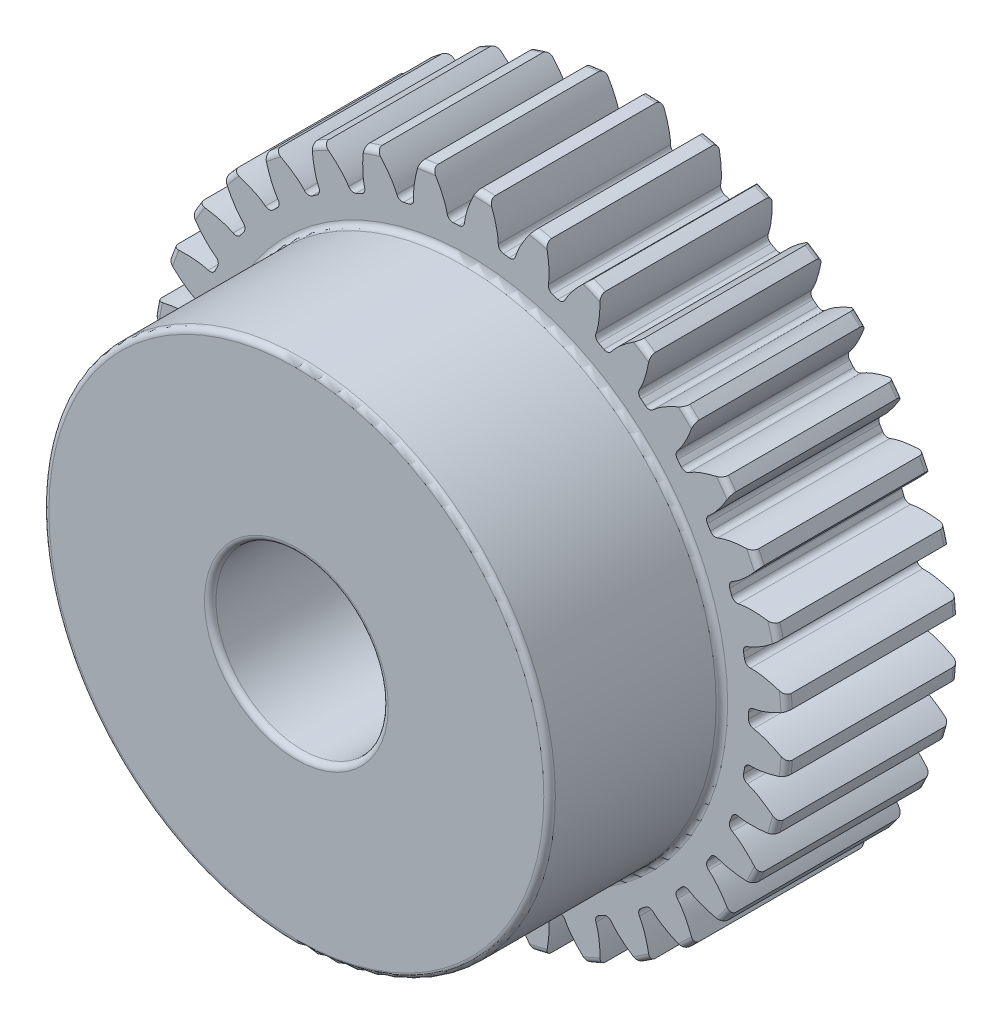
SolidWorks part; units mm, degrees
ref_plane "Front Plane" through (0, 0, 0) normal (0, 0, 1) x (1, 0, 0)
ref_plane "Top Plane" through (0, 0, 0) normal (0, 1, 0) x (1, 0, 0)
ref_plane "Right Plane" through (0, 0, 0) normal (1, 0, 0) x (0, 0, -1)
sketch "Sketch1" plane through (0, 0, 0) normal (0, 0, 1) x (1, 0, 0)
  line L0 (0, 0) -> (0, 22.225) construction
  line L1 (-7.143, 24.8248) -> (7.143, 19.6252) construction
  circle A0 centre (0, 0) radius 20.6375 construction
  circle A1 centre (0, 0) radius 23.495 construction
  circle A2 centre (0, 0) radius 22.225 construction
  circle A3 centre (0, 0) radius 20.8847 construction
  circle A4 centre (0, 0) radius 6.35 construction
  circle A5 centre (0, 0) radius 18.669 construction
  point P8 (254, 0)
  point P13 (444.5, 0)
  dimension "OD | Outside Diameter" = 46.99
  dimension "Root Diameter" = 41.275
  dimension "Gear Pitch Diameter" = 44.45
  dimension "Base Diameter" = 41.7693
  dimension "For Shaft Diameter" = 12.7
  dimension "Hub Diameter" = 37.338
  dimension "Pressure Angle" = 20
  dimension "Number of Teeth" = 889
  dimension "Gear Pitch | Diametral Pitch" = 508
sketch "Sketch2" plane through (0, 0, 0) normal (1, 0, 0) x (0, 0, -1)
  line L0 (-12.7, 0) -> (12.7, 0) construction
  line L1 (-12.7, 23.495) -> (12.7, 23.495) construction
  point P2 (0, 23.495)
  point P4 (0, 0)
  point P6 (0, 23.495)
  dimension "Overall Width" = 25.4
  dimension "Hub Width" = 12.7
  dimension "Face Width" = 12.7
sketch "Sketch3" plane through (0, 0, 0) normal (0, 0, 1) x (1, 0, 0)
  circle A0 centre (0, 0) radius 23.495
  circle A1 centre (0, 0) radius 23.495 construction
extrude "Boss-Extrude1" add sketch "Sketch3" against normal up to vertex (12.7 mm away) and the other way up to vertex (12.7 mm away) up to point (0, 0, -12.7) other way up to point (0, 0, 12.7)
sketch "Sketch5" plane through (0, 0, 0) normal (1, 0, 0) x (0, 0, -1)
  line L1 (-12.7, 23.495) -> (0, 23.495)
  line L2 (-12.7, 23.495) -> (-12.7, 18.669)
  line L3 (-12.7, 18.669) -> (0, 18.669)
  line L4 (0, 23.495) -> (0, 18.669)
  line L11 (12.7, 6.35) -> (-12.7, 6.35)
  line L12 (12.7, 6.35) -> (12.7, 0)
  line L13 (12.7, 0) -> (-12.7, 0)
  line L14 (-12.7, 6.35) -> (-12.7, 0)
  point P5 (0, 6.35)
  point P12 (0, 18.669)
revolve "Cut-Revolve1" cut sketch "Sketch5" angle 360 about L0
fillet "Fillet2" radius 0.4261 6 edges at (23.495, 0, -12.7) (6.35, 0, -12.7) (6.35, 0, 12.7) (18.669, 0, 0) (23.495, 0, 0) (18.669, 0, 12.7)
sketch "Sketch4" plane through (0, 0, 0) normal (0, 0, 1) x (1, 0, 0)
  line L0 (0, 0) -> (20.6282, 0.6185) construction
  line L2 (0, 0) -> (20.6282, -0.6185) construction
  line L4 (20.6282, 0.6185) -> (20.8753, 0.6259)
  line L5 (20.8753, -0.6259) -> (20.6282, -0.6185)
  arc A0 (20.6282, 0.6185) -> (20.6282, -0.6185) centre (0, 0) cw
  arc A3 (23.4383, 1.631) -> (23.4383, -1.631) centre (0, 0) cw
  circle A4 centre (0, 0) radius 23.495 construction
  spline S0 degree 4 poles (20.8753, 0.6259) (20.8794, 0.6261) (20.8909, 0.6267) (20.9126, 0.6284) (20.9479, 0.632) (20.993, 0.6376) (21.0511, 0.6462) (21.1194, 0.6581) (21.1944, 0.6729) (21.2759, 0.6908) (21.357, 0.7105) (21.4378, 0.7316) (21.5182, 0.7541) (21.6154, 0.783) (21.7317, 0.8199) (21.8673, 0.8665) (22.0206, 0.9233) (22.1763, 0.9855) (22.3291, 1.0501) (22.4829, 1.1195) (22.6314, 1.1894) (22.785, 1.2661) (22.9265, 1.3391) (23.0844, 1.4253) (23.2115, 1.4962) (23.3785, 1.5946) (23.4769, 1.6542) (23.5918, 1.7255) (23.6426, 1.7581) (23.674, 1.7781) knots 0 0 0 0 0 0.005377 0.015084 0.028532 0.04661 0.064855 0.092111 0.119476 0.146842 0.174209 0.201575 0.228941 0.256307 0.307035 0.361767 0.4165 0.471232 0.525964 0.580697 0.635429 0.690161 0.744894 0.799626 0.854358 0.909091 0.954545 1 1 1 1 1 construction
  spline S1 degree 4 poles (20.8753, 0.6259) (20.8794, 0.6261) (20.8909, 0.6267) (20.9126, 0.6284) (20.9479, 0.632) (20.993, 0.6376) (21.0511, 0.6462) (21.1194, 0.6581) (21.1944, 0.6729) (21.2759, 0.6908) (21.357, 0.7105) (21.4378, 0.7316) (21.5182, 0.7541) (21.6154, 0.783) (21.7317, 0.8199) (21.8673, 0.8665) (22.0206, 0.9233) (22.1763, 0.9855) (22.3291, 1.0501) (22.4829, 1.1195) (22.6314, 1.1894) (22.785, 1.2661) (22.9265, 1.3391) (23.0844, 1.4253) (23.2115, 1.4962) (23.3423, 1.5733) (23.4059, 1.6113) (23.4383, 1.631) knots 0 0 0 0 0 0.005377 0.015084 0.028532 0.04661 0.064855 0.092111 0.119476 0.146842 0.174209 0.201575 0.228941 0.256307 0.307035 0.361767 0.4165 0.471232 0.525964 0.580697 0.635429 0.690161 0.744894 0.799626 0.854358 0.909091 0.909091 0.909091 0.909091 0.909091
  spline S2 degree 4 poles (20.8753, -0.6259) (20.8794, -0.6261) (20.8909, -0.6267) (20.9126, -0.6284) (20.9479, -0.632) (20.993, -0.6376) (21.0511, -0.6462) (21.1194, -0.6581) (21.1944, -0.6729) (21.2759, -0.6908) (21.357, -0.7105) (21.4378, -0.7316) (21.5182, -0.7541) (21.6154, -0.783) (21.7317, -0.8199) (21.8673, -0.8665) (22.0206, -0.9233) (22.1763, -0.9855) (22.3291, -1.0501) (22.4829, -1.1195) (22.6314, -1.1894) (22.785, -1.2661) (22.9265, -1.3391) (23.0844, -1.4253) (23.2115, -1.4962) (23.3785, -1.5946) (23.4769, -1.6542) (23.5918, -1.7255) (23.6426, -1.7581) (23.674, -1.7781) knots 0 0 0 0 0 0.005377 0.015084 0.028532 0.04661 0.064855 0.092111 0.119476 0.146842 0.174209 0.201575 0.228941 0.256307 0.307035 0.361767 0.4165 0.471232 0.525964 0.580697 0.635429 0.690161 0.744894 0.799626 0.854358 0.909091 0.954545 1 1 1 1 1 construction
  spline S3 degree 4 poles (20.8753, -0.6259) (20.8794, -0.6261) (20.8909, -0.6267) (20.9126, -0.6284) (20.9479, -0.632) (20.993, -0.6376) (21.0511, -0.6462) (21.1194, -0.6581) (21.1944, -0.6729) (21.2759, -0.6908) (21.357, -0.7105) (21.4378, -0.7316) (21.5182, -0.7541) (21.6154, -0.783) (21.7317, -0.8199) (21.8673, -0.8665) (22.0206, -0.9233) (22.1763, -0.9855) (22.3291, -1.0501) (22.4829, -1.1195) (22.6314, -1.1894) (22.785, -1.2661) (22.9265, -1.3391) (23.0844, -1.4253) (23.2115, -1.4962) (23.3423, -1.5733) (23.4059, -1.6113) (23.4383, -1.631) knots 0 0 0 0 0 0.005377 0.015084 0.028532 0.04661 0.064855 0.092111 0.119476 0.146842 0.174209 0.201575 0.228941 0.256307 0.307035 0.361767 0.4165 0.471232 0.525964 0.580697 0.635429 0.690161 0.744894 0.799626 0.854358 0.909091 0.909091 0.909091 0.909091 0.909091
  dimension "D1" = 41.275
extrude "Cut-Extrude1" cut sketch "Sketch4" against normal through all both and the other way through all
fillet "Fillet1" radius 0.4261 2 edges at (20.6282, -0.6185, -6.35) (20.6282, 0.6185, -6.35)
pattern_circular "CirPattern1" count 35 over 360 about axis through (0, 0, 12.7) along (0, 0, -1) of "Cut-Extrude1", "Fillet1"
equation "\"Root Diameter@Sketch1\"=\"Root Diameter\""
equation "\"OD | Outside Diameter@Sketch1\"=\"Outside Diameter\""
equation "\"D1@CirPattern1\"=\"Number of Teeth\""
equation "\"Diametral Pitch\"=20"
equation "\"Number of Teeth\"= 35"
equation "\"Pressure Angle\"=20"
equation "\"Pitch Diameter\"= \"Number of Teeth\" / \"Diametral Pitch\""
equation "\"Base Diameter\"= \"Pitch Diameter\" * cos ( \"Pressure Angle\" )"
equation "\"Outside Diameter\"= ( \"Number of Teeth\" + 2 ) / \"Diametral Pitch\""
equation "\"Dedendum\"= 1.25 / \"Diametral Pitch\""
equation "\"Root Diameter\"= \"Pitch Diameter\" - ( 2 * \"Dedendum\" )"
equation "\"Pitch Angle\"= 360deg / \"Number of Teeth\""
equation "\"Alpha\"= sqr ( \"Pitch Diameter\" ^ 2 - \"Base Diameter\" ^ 2 ) / \"Base Diameter\" * 180 / PI - \"Pressure Angle\""
equation "\"Beta\"= ( \"Pitch Angle\" / 4 - \"Alpha\" )"
equation "\"Phi\"= sqr ( ( \"Outside Diameter\" / 2 ) ^ 2 - ( \"Base Diameter\" / 2 ) ^ 2 ) / ( \"Base Diameter\" / 2 )"
equation "\"Addendum\"= 1 / \"Diametral Pitch\""
equation "\"WorkingDepth\"= 2 / \"Diametral Pitch\""
equation "\"WholeDepth\"= 2.25 / \"Diametral Pitch\""
equation "\"Clearance\"= 0.25 / \"Diametral Pitch\""
equation "\"ToothThickness\"= ( pi * 2 ) / \"Diametral Pitch\""
equation "\"CircularPitch\"= pi / \"Diametral Pitch\""
equation "\"Number of Teeth@Sketch1\"=\"Number of Teeth\""
equation "\"Gear Pitch | Diametral Pitch@Sketch1\"=\"Diametral Pitch\""
equation "\"Pressure Angle@Sketch1\"=\"Pressure Angle\""
equation "\"Gear Pitch Diameter@Sketch1\"=\"Pitch Diameter\""
equation "\"Base Diameter@Sketch1\"=\"Base Diameter\""
equation "\"Fillet\"= \"Clearance\" * cos ( \"Pressure Angle\" ) * tan ( ( 90 + \"Pressure Angle\" ) / 2 )"
equation "\"D1@Fillet1\"=\"Fillet\""
equation "\"D1@Sketch4\"=if( \"Base Diameter\">\"Root Diameter\",\"Root Diameter\",\"Base Diameter\"-.00001)"
equation "\"D1@Fillet2\"=\"Fillet\""
